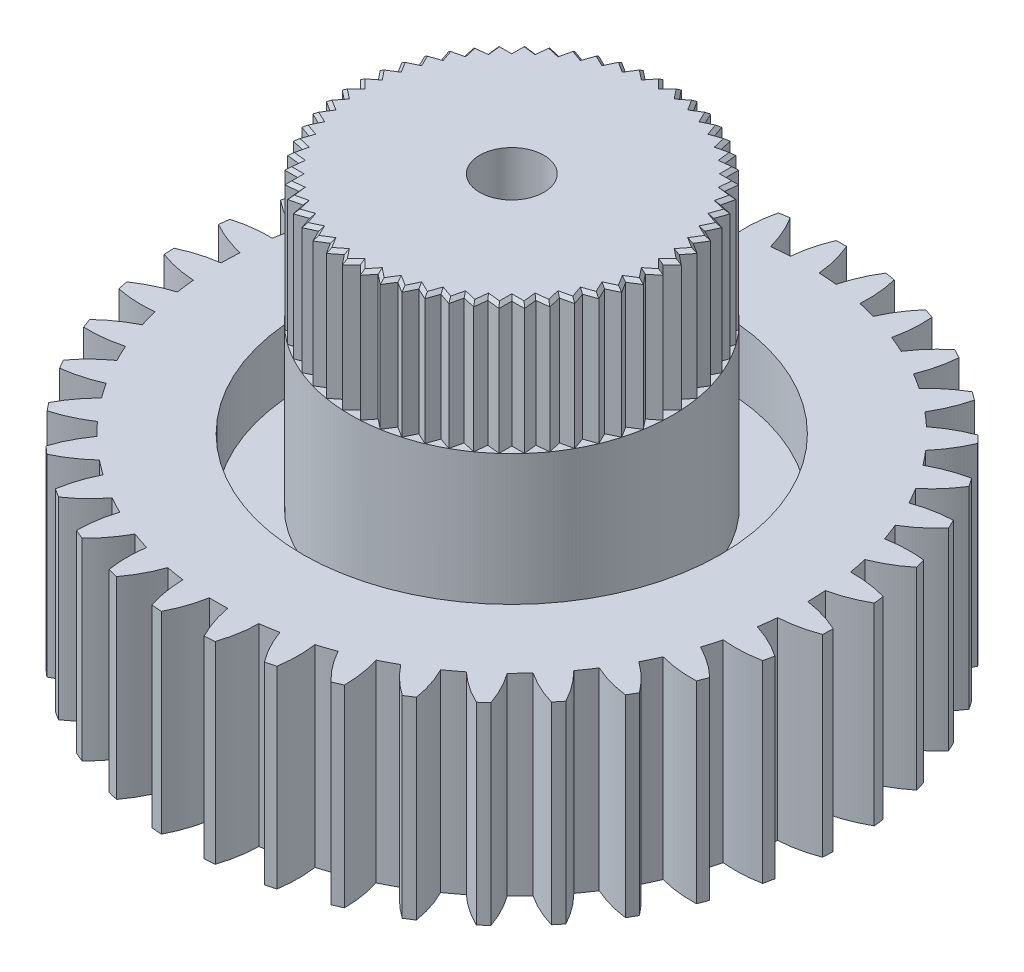
SolidWorks part; units mm, degrees
note: The reader was unsure of these and kept them because the rebuilt part matched: shared geometry of "Sketch2<3>".
ref_plane "Front Plane" through (0, 0, 0) normal (0, 0, 1) x (1, 0, 0)
ref_plane "Top Plane" through (0, 0, 0) normal (0, 1, 0) x (1, 0, 0)
ref_plane "Right Plane" through (0, 0, 0) normal (1, 0, 0) x (0, 0, -1)
sketch "Sketch1" plane through (0, 0, 0) normal (0, 1, 0) x (1, 0, 0)
  line L0 (0, 0) -> (0, 5.125) construction
  circle A0 centre (0, 0) radius 0.5
  circle A1 centre (0, 0) radius 4.56
  arc A2 (-0.743, 5.0708) -> (-0.901, 5.0452) centre (0, 0) ccw
  arc A3 (-0.225, 4.5544) -> (-0.08, 5.1244) centre (1.7157, 4.3641) cw
  arc A4 (0.225, 4.5544) -> (0.08, 5.1244) centre (-1.7157, 4.3641) ccw
  arc A5 (0.5085, 4.5316) -> (0.743, 5.0708) centre (2.3935, 4.0324) cw
  arc A6 (0.9527, 4.4594) -> (0.901, 5.0452) centre (-0.9934, 4.5828) ccw
  arc A7 (1.2288, 4.3913) -> (1.5468, 4.886) centre (3.0094, 3.5962) cw
  arc A8 (1.6557, 4.2488) -> (1.6986, 4.8353) centre (-0.2454, 4.6828) ccw
  arc A9 (1.9173, 4.1373) -> (2.3106, 4.5746) centre (3.5473, 3.0669) cw
  arc A10 (2.3158, 3.9282) -> (2.4523, 4.5002) centre (0.5089, 4.6615) ccw
  arc A11 (2.5562, 3.7762) -> (3.0145, 4.1447) centre (3.9933, 2.4582) cw
  arc A12 (2.9159, 3.5059) -> (3.1424, 4.0486) centre (1.2501, 4.5195) ccw
  arc A13 (3.1288, 3.3172) -> (3.6403, 3.6075) centre (4.3359, 1.7858) cw
  arc A14 (3.4405, 2.9927) -> (3.7511, 3.4921) centre (1.9589, 4.2605) ccw
  arc A15 (3.6204, 2.7724) -> (4.1718, 2.9768) centre (4.5662, 1.0671) cw
  arc A16 (3.876, 2.402) -> (4.2627, 2.8451) centre (2.617, 3.8911) ccw
  arc A17 (4.0183, 2.1557) -> (4.5953, 2.2691) centre (4.6783, 0.3208) cw
  arc A18 (4.2112, 1.7492) -> (4.6639, 2.1245) centre (3.2073, 3.4209) ccw
  arc A19 (4.312, 1.4832) -> (4.8998, 1.5025) centre (4.6691, -0.4338) cw
  arc A20 (4.4372, 1.051) -> (4.9443, 1.3488) centre (3.7145, 2.8621) ccw
  arc A21 (4.4941, 0.7723) -> (5.0774, 0.6971) centre (4.5391, -1.1771) cw
  arc A22 (4.5484, 0.3256) -> (5.0967, 0.5383) centre (4.1255, 2.2292) ccw
  arc A23 (4.5598, 0.0414) -> (5.1234, -0.1264) centre (4.2915, -1.89) cw
  arc A24 (4.5417, -0.4082) -> (5.117, -0.2863) centre (4.4297, 1.5386) ccw
  arc A25 (4.5074, -0.6906) -> (5.0368, -0.9466) centre (3.9327, -2.554) cw
  arc A26 (4.4174, -1.1315) -> (5.0048, -1.1034) centre (4.6191, 0.8081) ccw
  arc A27 (4.3383, -1.4047) -> (4.8197, -1.7423) centre (3.4721, -3.1517) cw
  arc A28 (4.1787, -1.8254) -> (4.763, -1.8919) centre (4.6889, 0.0567) ccw
  arc A29 (4.0568, -2.0824) -> (4.4778, -2.4929) centre (2.9216, -3.6679) cw
  arc A30 (3.8318, -2.4721) -> (4.3978, -2.6315) centre (4.6373, -0.6962) ccw
  arc A31 (3.6702, -2.7062) -> (4.02, -3.1789) centre (2.2954, -4.089) cw
  arc A32 (3.3856, -3.0547) -> (3.9188, -3.3029) centre (4.4655, -1.4311) ccw
  arc A33 (3.1886, -3.2598) -> (3.458, -3.7826) centre (1.6097, -4.4043) cw
  arc A34 (2.8517, -3.5583) -> (3.3382, -3.8887) centre (4.1782, -2.1289) ccw
  arc A35 (2.6244, -3.7291) -> (2.8064, -4.2883) centre (0.8824, -4.6055) cw
  arc A36 (2.244, -3.9696) -> (2.6712, -4.3738) centre (3.7826, -2.7715) ccw
  arc A37 (1.9922, -4.1018) -> (2.0822, -4.683) centre (0.1322, -4.6874) cw
  arc A38 (1.5782, -4.2782) -> (1.935, -4.7457) centre (3.289, -3.3424) ccw
  arc A39 (1.3084, -4.3683) -> (1.304, -4.9563) centre (-0.6214, -4.6479) cw
  arc A40 (0.8715, -4.4759) -> (1.1487, -4.9946) centre (2.7102, -3.8267) ccw
  arc A41 (0.5908, -4.5216) -> (0.4921, -5.1013) centre (-1.359, -4.488) cw
  arc A42 (0.1422, -4.5578) -> (0.3326, -5.1142) centre (2.0613, -4.2119) ccw
  arc A43 (-0.1422, -4.5578) -> (-0.3326, -5.1142) centre (-2.0613, -4.2119) cw
  arc A44 (-0.5908, -4.5216) -> (-0.4921, -5.1013) centre (1.359, -4.488) ccw
  arc A45 (-0.8715, -4.4759) -> (-1.1487, -4.9946) centre (-2.7102, -3.8267) cw
  arc A46 (-1.3084, -4.3683) -> (-1.304, -4.9563) centre (0.6214, -4.6479) ccw
  arc A47 (-1.5782, -4.2782) -> (-1.935, -4.7457) centre (-3.289, -3.3424) cw
  arc A48 (-1.9922, -4.1018) -> (-2.0822, -4.683) centre (-0.1322, -4.6874) ccw
  arc A49 (-2.244, -3.9696) -> (-2.6712, -4.3738) centre (-3.7826, -2.7715) cw
  arc A50 (-2.6244, -3.7291) -> (-2.8064, -4.2883) centre (-0.8824, -4.6055) ccw
  arc A51 (-2.8517, -3.5583) -> (-3.3382, -3.8887) centre (-4.1782, -2.1289) cw
  arc A52 (-3.1886, -3.2598) -> (-3.458, -3.7826) centre (-1.6097, -4.4043) ccw
  arc A53 (-3.3856, -3.0547) -> (-3.9188, -3.3029) centre (-4.4655, -1.4311) cw
  arc A54 (-3.6702, -2.7062) -> (-4.02, -3.1789) centre (-2.2954, -4.089) ccw
  arc A55 (-3.8318, -2.4721) -> (-4.3978, -2.6315) centre (-4.6373, -0.6962) cw
  arc A56 (-4.0568, -2.0824) -> (-4.4778, -2.4929) centre (-2.9216, -3.6679) ccw
  arc A57 (-4.1787, -1.8254) -> (-4.763, -1.8919) centre (-4.6889, 0.0567) cw
  arc A58 (-4.3383, -1.4047) -> (-4.8197, -1.7423) centre (-3.4721, -3.1517) ccw
  arc A59 (-4.4174, -1.1315) -> (-5.0048, -1.1034) centre (-4.6191, 0.8081) cw
  arc A60 (-4.5074, -0.6906) -> (-5.0368, -0.9466) centre (-3.9327, -2.554) ccw
  arc A61 (-4.5417, -0.4082) -> (-5.117, -0.2863) centre (-4.4297, 1.5386) cw
  arc A62 (-4.5598, 0.0414) -> (-5.1234, -0.1264) centre (-4.2915, -1.89) ccw
  arc A63 (-4.5484, 0.3256) -> (-5.0967, 0.5383) centre (-4.1255, 2.2292) cw
  arc A64 (-4.4941, 0.7723) -> (-5.0774, 0.6971) centre (-4.5391, -1.1771) ccw
  arc A65 (-4.4372, 1.051) -> (-4.9443, 1.3488) centre (-3.7145, 2.8621) cw
  arc A66 (-4.312, 1.4832) -> (-4.8998, 1.5025) centre (-4.6691, -0.4338) ccw
  arc A67 (-4.2112, 1.7492) -> (-4.6639, 2.1245) centre (-3.2073, 3.4209) cw
  arc A68 (-4.0183, 2.1557) -> (-4.5953, 2.2691) centre (-4.6783, 0.3208) ccw
  arc A69 (-3.876, 2.402) -> (-4.2627, 2.8451) centre (-2.617, 3.8911) cw
  arc A70 (-3.6204, 2.7724) -> (-4.1718, 2.9768) centre (-4.5662, 1.0671) ccw
  arc A71 (-3.4405, 2.9927) -> (-3.7511, 3.4921) centre (-1.9589, 4.2605) cw
  arc A72 (-3.1288, 3.3172) -> (-3.6403, 3.6075) centre (-4.3359, 1.7858) ccw
  arc A73 (-2.9159, 3.5059) -> (-3.1424, 4.0486) centre (-1.2501, 4.5195) cw
  arc A74 (-2.5562, 3.7762) -> (-3.0145, 4.1447) centre (-3.9933, 2.4582) ccw
  arc A75 (-2.3158, 3.9282) -> (-2.4523, 4.5002) centre (-0.5089, 4.6615) cw
  arc A76 (-1.9173, 4.1373) -> (-2.3106, 4.5746) centre (-3.5473, 3.0669) ccw
  arc A77 (-1.6557, 4.2488) -> (-1.6986, 4.8353) centre (0.2454, 4.6828) cw
  arc A78 (-1.2288, 4.3913) -> (-1.5468, 4.886) centre (-3.0094, 3.5962) ccw
  arc A79 (-0.9527, 4.4594) -> (-0.901, 5.0452) centre (0.9934, 4.5828) cw
  arc A80 (-0.5085, 4.5316) -> (-0.743, 5.0708) centre (-2.3935, 4.0324) ccw
  arc A81 (-1.5468, 4.886) -> (-1.6986, 4.8353) centre (0, 0) ccw
  arc A82 (-2.3106, 4.5746) -> (-2.4523, 4.5002) centre (0, 0) ccw
  arc A83 (-3.0145, 4.1447) -> (-3.1424, 4.0486) centre (0, 0) ccw
  arc A84 (-3.6403, 3.6075) -> (-3.7511, 3.4921) centre (0, 0) ccw
  arc A85 (-4.1718, 2.9768) -> (-4.2627, 2.8451) centre (0, 0) ccw
  arc A86 (-4.5953, 2.2691) -> (-4.6639, 2.1245) centre (0, 0) ccw
  arc A87 (-4.8998, 1.5025) -> (-4.9443, 1.3488) centre (0, 0) ccw
  arc A88 (-5.0774, 0.6971) -> (-5.0967, 0.5383) centre (0, 0) ccw
  arc A89 (0.08, 5.1244) -> (-0.08, 5.1244) centre (0, 0) ccw
  arc A90 (0.901, 5.0452) -> (0.743, 5.0708) centre (0, 0) ccw
  arc A91 (1.6986, 4.8353) -> (1.5468, 4.886) centre (0, 0) ccw
  arc A92 (2.4523, 4.5002) -> (2.3106, 4.5746) centre (0, 0) ccw
  arc A93 (3.1424, 4.0486) -> (3.0145, 4.1447) centre (0, 0) ccw
  arc A94 (3.7511, 3.4921) -> (3.6403, 3.6075) centre (0, 0) ccw
  arc A95 (4.2627, 2.8451) -> (4.1718, 2.9768) centre (0, 0) ccw
  arc A96 (4.6639, 2.1245) -> (4.5953, 2.2691) centre (0, 0) ccw
  arc A97 (4.9443, 1.3488) -> (4.8998, 1.5025) centre (0, 0) ccw
  arc A98 (5.0967, 0.5383) -> (5.0774, 0.6971) centre (0, 0) ccw
  arc A99 (5.117, -0.2863) -> (5.1234, -0.1264) centre (0, 0) ccw
  arc A100 (5.0048, -1.1034) -> (5.0368, -0.9466) centre (0, 0) ccw
  arc A101 (4.763, -1.8919) -> (4.8197, -1.7423) centre (0, 0) ccw
  arc A102 (4.3978, -2.6315) -> (4.4778, -2.4929) centre (0, 0) ccw
  arc A103 (3.9188, -3.3029) -> (4.02, -3.1789) centre (0, 0) ccw
  arc A104 (3.3382, -3.8887) -> (3.458, -3.7826) centre (0, 0) ccw
  arc A105 (2.6712, -4.3738) -> (2.8064, -4.2883) centre (0, 0) ccw
  arc A106 (1.935, -4.7457) -> (2.0822, -4.683) centre (0, 0) ccw
  arc A107 (1.1487, -4.9946) -> (1.304, -4.9563) centre (0, 0) ccw
  arc A108 (0.3326, -5.1142) -> (0.4921, -5.1013) centre (0, 0) ccw
  arc A109 (-0.4921, -5.1013) -> (-0.3326, -5.1142) centre (0, 0) ccw
  arc A110 (-1.304, -4.9563) -> (-1.1487, -4.9946) centre (0, 0) ccw
  arc A111 (-2.0822, -4.683) -> (-1.935, -4.7457) centre (0, 0) ccw
  arc A112 (-2.8064, -4.2883) -> (-2.6712, -4.3738) centre (0, 0) ccw
  arc A113 (-3.458, -3.7826) -> (-3.3382, -3.8887) centre (0, 0) ccw
  arc A114 (-4.02, -3.1789) -> (-3.9188, -3.3029) centre (0, 0) ccw
  arc A115 (-4.4778, -2.4929) -> (-4.3978, -2.6315) centre (0, 0) ccw
  arc A116 (-4.8197, -1.7423) -> (-4.763, -1.8919) centre (0, 0) ccw
  arc A117 (-5.1234, -0.1264) -> (-5.117, -0.2863) centre (0, 0) ccw
  arc A118 (-5.0368, -0.9466) -> (-5.0048, -1.1034) centre (0, 0) ccw
  point P242 (0, 0)
  dimension "D1" = 10.25
  dimension "D2" = 9.12
  dimension "D3" = 1
  dimension "D4" = 1.95
  dimension "D5" = 0.225
  dimension "D6" = 0.08
  dimension "D7" = 39
extrude "Boss-Extrude3" add sketch "Sketch1" along normal blind 3
sketch "Sketch2" plane through (0, 3, 0) normal (0, 1, 0) x (1, 0, 0)
  circle A0 centre (0, 0) radius 3.25
  circle A1 centre (0, 0) radius 2.5
  dimension "D1" = 6.5
  dimension "D2" = 5
extrude "Cut-Extrude1" cut sketch "Sketch2" against normal blind 1 contours A1 | A0 A1
extrude "Boss-Extrude4" add sketch "Sketch2<3>" along normal blind 3.5 and the other way up to surface (1 mm away) contours A1 other way up to face at (0, 2, 0.5)
sketch "Sketch2<3>" plane through (0, 3, 0) normal (0, 1, 0) x (1, 0, 0) same geometry as "Sketch2"
sketch "Sketch3" plane through (0, 6.5, 0) normal (0, 1, 0) x (1, 0, 0)
  line L0 (0, 0) -> (0, 2.5) construction
  line L1 (-0.1414, 2.496) -> (0, 2.3546)
  line L2 (0, 2.3546) -> (0.1414, 2.496)
  circle A0 centre (0, 0) radius 2.5 construction
  circle A1 centre (0, 0) radius 2.5
  circle M1 centre (0, 0) radius 2.5
  dimension "D1" = 0.2
extrude "Cut-Extrude2" cut sketch "Sketch3" against normal blind 2 contours L1 L0 A1 | L0 L2 M1
pattern_circular "CirPattern1" count 56 over 360 about axis through (0, 0, 0) along (0, 1, 0) of "Cut-Extrude2"
chamfer "Chamfer1" distance 0.05 angle 45 112 edges at (-0.07, 6.5, -2.4246) (0.07, 6.5, -2.4246) (0.2019, 6.5, -2.4172) (0.3411, 6.5, -2.4015) (0.4712, 6.5, -2.3794) (0.6078, 6.5, -2.3482) (0.7347, 6.5, -2.3117) (0.8669, 6.5, -2.2654) (0.9889, 6.5, -2.2149) (1.1151, 6.5, -2.1541) (1.2307, 6.5, -2.0903) (1.3493, 6.5, -2.0157) (1.457, 6.5, -1.9393) (1.5665, 6.5, -1.852) (1.6649, 6.5, -1.764) (1.764, 6.5, -1.6649) (1.852, 6.5, -1.5665) (1.9393, 6.5, -1.457) (2.0157, 6.5, -1.3493) (2.0903, 6.5, -1.2307) (2.1541, 6.5, -1.1151) (2.2149, 6.5, -0.9889) (2.2654, 6.5, -0.8669) (2.3117, 6.5, -0.7347) (2.3482, 6.5, -0.6078) (2.3794, 6.5, -0.4712) (2.4015, 6.5, -0.3411) (2.4172, 6.5, -0.2019) (2.4246, 6.5, -0.07) (2.4246, 6.5, 0.07) (2.4172, 6.5, 0.2019) (2.4015, 6.5, 0.3411) (2.3794, 6.5, 0.4712) (2.3482, 6.5, 0.6078) (2.3117, 6.5, 0.7347) (2.2654, 6.5, 0.8669) (2.2149, 6.5, 0.9889) (2.1541, 6.5, 1.1151) (2.0903, 6.5, 1.2307) (2.0157, 6.5, 1.3493) (1.9393, 6.5, 1.457) (1.852, 6.5, 1.5665) (1.764, 6.5, 1.6649) (1.6649, 6.5, 1.764) (1.5665, 6.5, 1.852) (1.457, 6.5, 1.9393) (1.3493, 6.5, 2.0157) (1.2307, 6.5, 2.0903) (1.1151, 6.5, 2.1541) (0.9889, 6.5, 2.2149) (0.8669, 6.5, 2.2654) (0.7347, 6.5, 2.3117) (0.6078, 6.5, 2.3482) (0.4712, 6.5, 2.3794) (0.3411, 6.5, 2.4015) (0.2019, 6.5, 2.4172) (0.07, 6.5, 2.4246) (-0.07, 6.5, 2.4246) (-0.2019, 6.5, 2.4172) (-0.3411, 6.5, 2.4015) (-0.4712, 6.5, 2.3794) (-0.6078, 6.5, 2.3482) (-0.7347, 6.5, 2.3117) (-0.8669, 6.5, 2.2654) (-0.9889, 6.5, 2.2149) (-1.1151, 6.5, 2.1541) (-1.2307, 6.5, 2.0903) (-1.3493, 6.5, 2.0157) (-1.457, 6.5, 1.9393) (-1.5665, 6.5, 1.852) (-1.6649, 6.5, 1.764) (-1.764, 6.5, 1.6649) (-1.852, 6.5, 1.5665) (-1.9393, 6.5, 1.457) (-2.0157, 6.5, 1.3493) (-2.0903, 6.5, 1.2307) (-2.1541, 6.5, 1.1151) (-2.2149, 6.5, 0.9889) (-2.2654, 6.5, 0.8669) (-2.3117, 6.5, 0.7347) (-2.3482, 6.5, 0.6078) (-2.3794, 6.5, 0.4712) (-2.4015, 6.5, 0.3411) (-2.4172, 6.5, 0.2019) (-2.4246, 6.5, 0.07) (-2.4246, 6.5, -0.07) (-2.4172, 6.5, -0.2019) (-2.4015, 6.5, -0.3411) (-2.3794, 6.5, -0.4712) (-2.3482, 6.5, -0.6078) (-2.3117, 6.5, -0.7347) (-2.2654, 6.5, -0.8669) (-2.2149, 6.5, -0.9889) (-2.1541, 6.5, -1.1151) (-2.0903, 6.5, -1.2307) (-2.0157, 6.5, -1.3493) (-1.9393, 6.5, -1.457) (-1.852, 6.5, -1.5665) (-1.764, 6.5, -1.6649) (-1.6649, 6.5, -1.764) (-1.5665, 6.5, -1.852) (-1.457, 6.5, -1.9393) (-1.3493, 6.5, -2.0157) (-1.2307, 6.5, -2.0903) (-1.1151, 6.5, -2.1541) (-0.9889, 6.5, -2.2149) (-0.8669, 6.5, -2.2654) (-0.7347, 6.5, -2.3117) (-0.6078, 6.5, -2.3482) (-0.4712, 6.5, -2.3794) (-0.3411, 6.5, -2.4015) (-0.2019, 6.5, -2.4172)
sketch "Sketch4" plane through (0, 2, 0) normal (0, -1, 0) x (1, 0, 0)
  circle A1 centre (0, 0) radius 0.5
  circle A2 centre (0, 0) radius 0.5
  dimension "D1" = 0
extrude "Cut-Extrude3" cut sketch "Sketch4" against normal up to next
